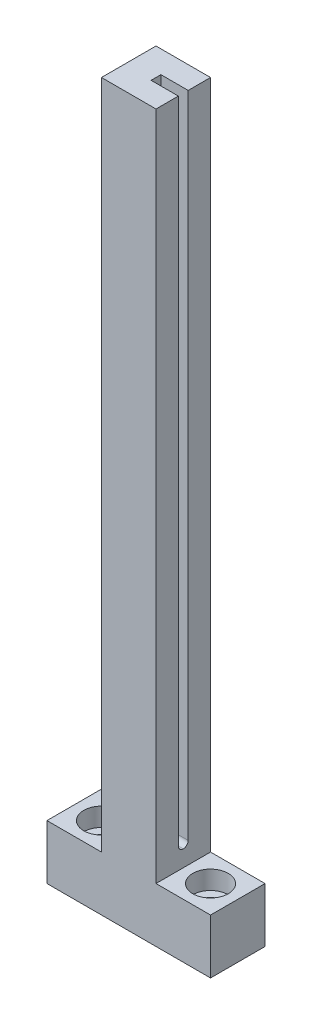
SolidWorks part; units mm, degrees
material "Polyetheretherketone (PEEK)"
ref_plane "Front Plane" through (0, 0, 0) normal (0, 0, 1) x (1, 0, 0)
ref_plane "Top Plane" through (0, 0, 0) normal (0, 1, 0) x (1, 0, 0)
ref_plane "Right Plane" through (0, 0, 0) normal (1, 0, 0) x (0, 0, -1)
sketch "Sketch1" plane through (0, 0, 0) normal (0, 1, 0) x (1, 0, 0)
  line L1 (-5, 5) -> (5, 5)
  line L2 (-5, 5) -> (-5, -5)
  line L3 (-5, -5) -> (5, -5)
  line L4 (5, 5) -> (5, -5)
  line L5 (-5, 5) -> (5, -5) construction
  line L6 (-5, -5) -> (5, 5) construction
  point P0 (0, 0)
  dimension "D1" = 10
  dimension "D2" = 10
extrude "Boss-Extrude1" add sketch "Sketch1" along normal blind 133
sketch "Sketch3" plane through (5, 0, 0) normal (1, 0, 0) x (0, 0, -1)
  line L0 (-5, 133) -> (5, 133) construction
  line L1 (-0.9, 133) -> (0.9, 133)
  line L2 (-0.9, 133) -> (-0.9, 13)
  line L3 (-0.9, 13) -> (0.9, 13)
  line L4 (0.9, 133) -> (0.9, 13)
  line L5 (0, 16.5) -> (0, -16.5) construction
  point P6 (0, 13)
  dimension "D1" = 1.8
  dimension "D2" = 120
extrude "Cut-Extrude1" cut sketch "Sketch3" against normal blind 5
fillet "Fillet1" radius 0.9 2 edges at (2.5, 13, 0.9) (2.5, 13, -0.9)
sketch "Sketch4" plane through (0, 0, 0) normal (1, 0, 0) x (0, 0, -1)
  line L0 (0, 5.5) -> (0, -5.5) construction
  line L1 (-5, 0) -> (5, 0)
  line L2 (-5, 0) -> (-5, 10)
  line L3 (-5, 10) -> (5, 10)
  line L4 (5, 0) -> (5, 10)
  line L5 (-5, 133) -> (-5, 0) construction
  line L6 (-5, 0) -> (5, 0) construction
  point P4 (0, 0)
  dimension "D1" = 10
extrude "Boss-Extrude3" add sketch "Sketch4" along normal mid plane 30
hole_wizard "CBORE for M3 Hex Socket Head Cap Screw1" positions "3DSketch1" profile "Sketch5" counterbore size "M3" standard "ISO" end condition through all
sketch3d "3DSketch1"
  line L0 (15, 10, 5) -> (5, 10, 5) construction
  point P0 (10, 10, 0)
  point P3 (0, 0, 0)
  point P4 (0, 0, 0)
  point P7 (10, 10, 5)
sketch "Sketch5" plane through (10, 10, 0) normal (1, 0, 0) x (0, 0, 1)
  line L0 (0, 0) -> (0, 10)
  line L1 (0, 10) -> (1.7, 10)
  line L3 (1.7, 10) -> (1.7, 3.4)
  line L4 (1.7, 3.4) -> (3.25, 3.4)
  line L5 (3.25, 3.4) -> (3.25, 0)
  line L7 (3.25, 0) -> (0, 0)
  line L11 (0, -6.35) -> (0, 107.95) construction
  dimension "Thru Hole Dia." = 3.4
  dimension "Thru Hole Depth" = 10
  dimension "C'Bore Dia." = 6.5
  dimension "C'Bore Depth" = 3.4
mirror "Mirror1" about plane through (0, 0, 0) normal (1, 0, 0) of "CBORE for M3 Hex Socket Head Cap Screw1"
hole_wizard "Ø1.0mm Dowel Hole1" positions "3DSketch2" profile "Sketch6" hole size "Ø1.0" standard "ISO"
sketch3d "3DSketch2"
  point P0 (0, 0, 0)
  point P3 (0, 0, 0)
  point P4 (0, 0, 0)
sketch "Sketch6" plane through (0, 0, 0) normal (1, 0, 0) x (0, 0, -1)
  line L0 (0, 0) -> (0, 8.3004)
  line L1 (0, 8.3004) -> (0.5, 8)
  line L2 (0.5, 8) -> (0.5, 0)
  line L5 (0.5, 0) -> (0, 0)
  line L10 (0, 8.3004) -> (-0.5, 8) construction
  line L11 (0, -6.35) -> (0, 107.95) construction
  dimension "Hole Dia." = 1
  dimension "Hole Depth" = 8
  dimension "Drill Angle" = 118
